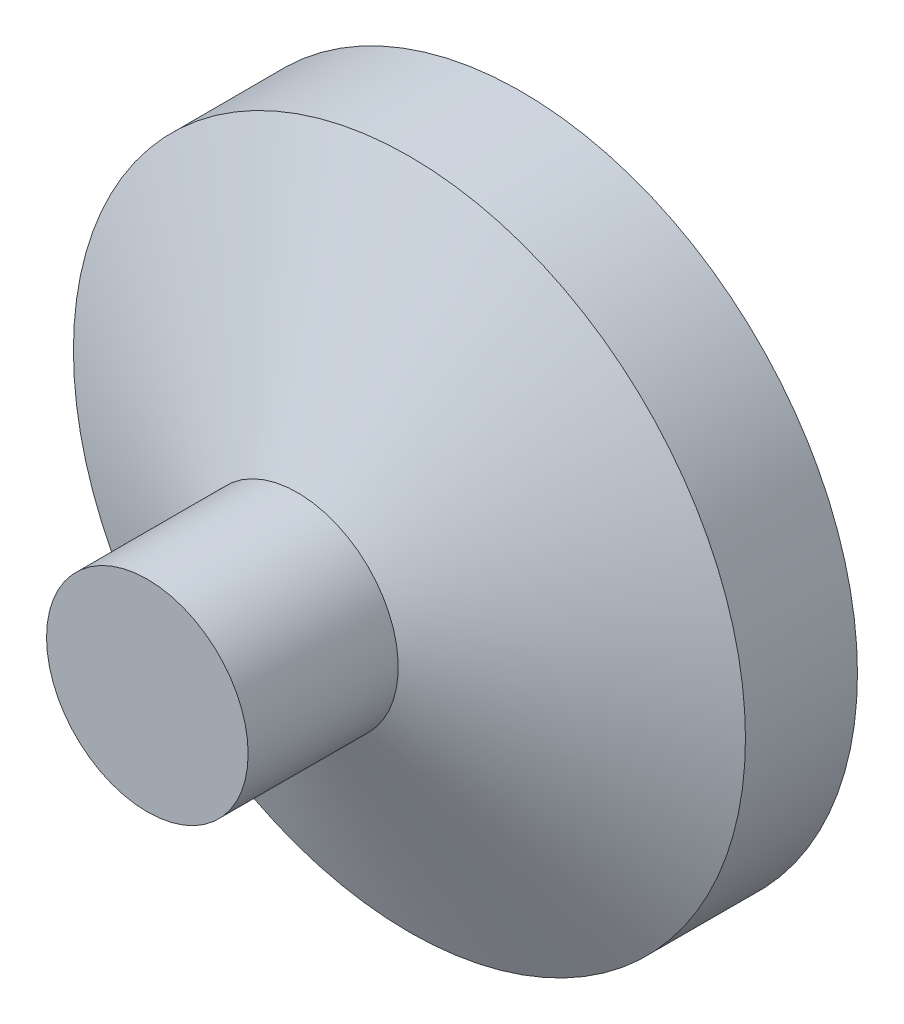
SolidWorks part; units mm, degrees
note: The reader was unsure of these and kept them because the rebuilt part matched: shared geometry of "Sketch3<2>".
ref_plane "Front Plane" through (0, 0, 0) normal (0, 0, 1) x (1, 0, 0)
ref_plane "Top Plane" through (0, 0, 0) normal (0, 1, 0) x (1, 0, 0)
ref_plane "Right Plane" through (0, 0, 0) normal (1, 0, 0) x (0, 0, -1)
sketch "Sketch1" plane through (0, 0, 0) normal (0, 0, 1) x (1, 0, 0)
  line L1 (0, 10) -> (0, 0) construction
  line L2 (0, 0) -> (8.6603, -5) construction
  line L3 (0, 0) -> (-8.6603, -5) construction
  circle A1 centre (0, 10) radius 1
  circle A5 centre (-8.6603, -5) radius 1
  circle A6 centre (8.6603, -5) radius 1
  dimension "D2" = 2
  dimension "D3" = 10
sketch "Sketch2" plane through (0, 0, 0) normal (0, 0, 1) x (1, 0, 0)
  line L0 (0, 0) -> (8.6603, -5) construction
  circle A0 centre (0, 0) radius 15
  dimension "D1" = 30
ref_plane "Plane1" through (0, 0, 5) normal (0, 0, 1) x (1, 0, 0)
sketch "Sketch3" plane through (0, 0, 5) normal (0, 0, 1) x (1, 0, 0)
  circle A0 centre (0, 0) radius 4.5
  dimension "D1" = 9
extrude "Boss-Extrude2" add sketch "Sketch2" against normal blind 5
loft "Loft1" add profiles "Sketch3" section "Sketch3" section edge at (15, 0, 0)
extrude "Boss-Extrude3" add sketch "Sketch3<2>" along normal blind 6.7
sketch "Sketch3<2>" plane through (0, 0, 5) normal (0, 0, 1) x (1, 0, 0) same geometry as "Sketch3"
extrude "Cut-Extrude1" cut sketch "Sketch1" against normal through all
